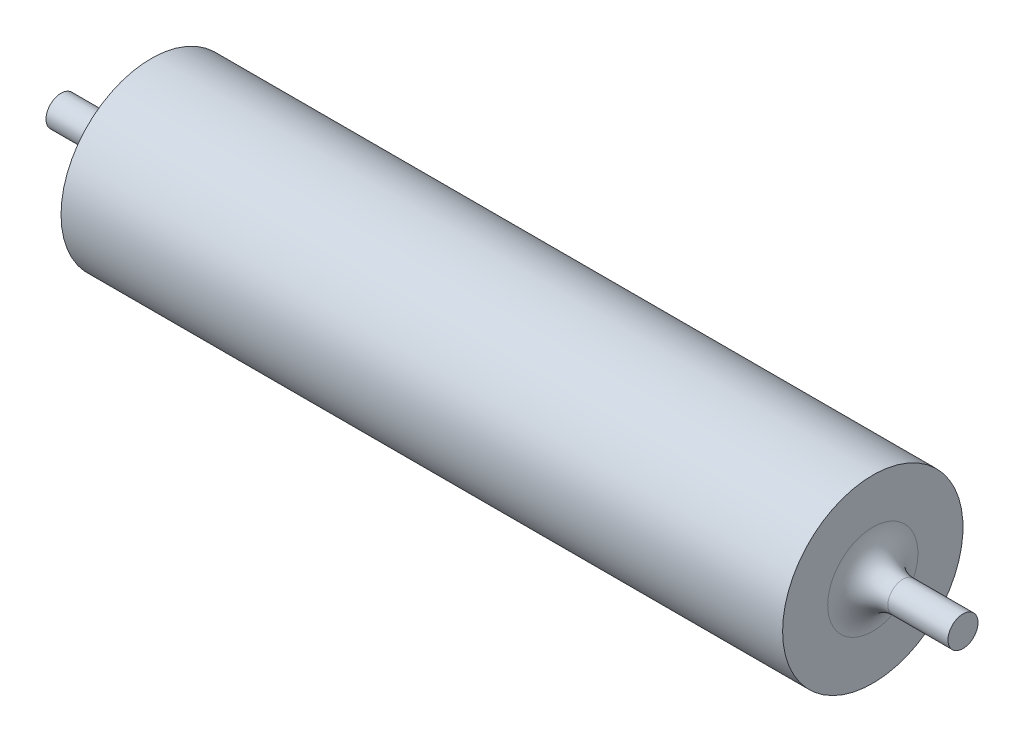
SolidWorks part; units mm, degrees
ref_plane "Plan de face" through (0, 0, 0) normal (0, 0, 1) x (1, 0, 0)
ref_plane "Plan de dessus" through (0, 0, 0) normal (0, 1, 0) x (1, 0, 0)
ref_plane "Plan de droite" through (0, 0, 0) normal (1, 0, 0) x (0, 0, -1)
sketch "Esquisse1" plane through (0, 0, 0) normal (0, 0, 1) x (1, 0, 0)
  line L0 (-81.1413, 0) -> (75.2437, 0) construction
  line L1 (-75, 0) -> (-75, 2.5)
  line L2 (-75, 2.5) -> (-60, 2.5)
  line L3 (-60, 2.5) -> (-60, 15)
  line L4 (-60, 15) -> (60, 15)
  line L5 (-75, 0) -> (75, 0)
  line L6 (0, 15) -> (0, 0) construction
  line L7 (60, 2.5) -> (60, 15)
  line L8 (75, 2.5) -> (60, 2.5)
  line L9 (75, 0) -> (75, 2.5)
  dimension "D1" = 75
  dimension "D2" = 15
  dimension "D3" = 2.5
  dimension "D4" = 15
revolve "Révolution1" add sketch "Esquisse1" angle 360 about L5
fillet "Congé1" radius 5 2 edges at (60, 0, 2.5) (-60, 0, 2.5)
